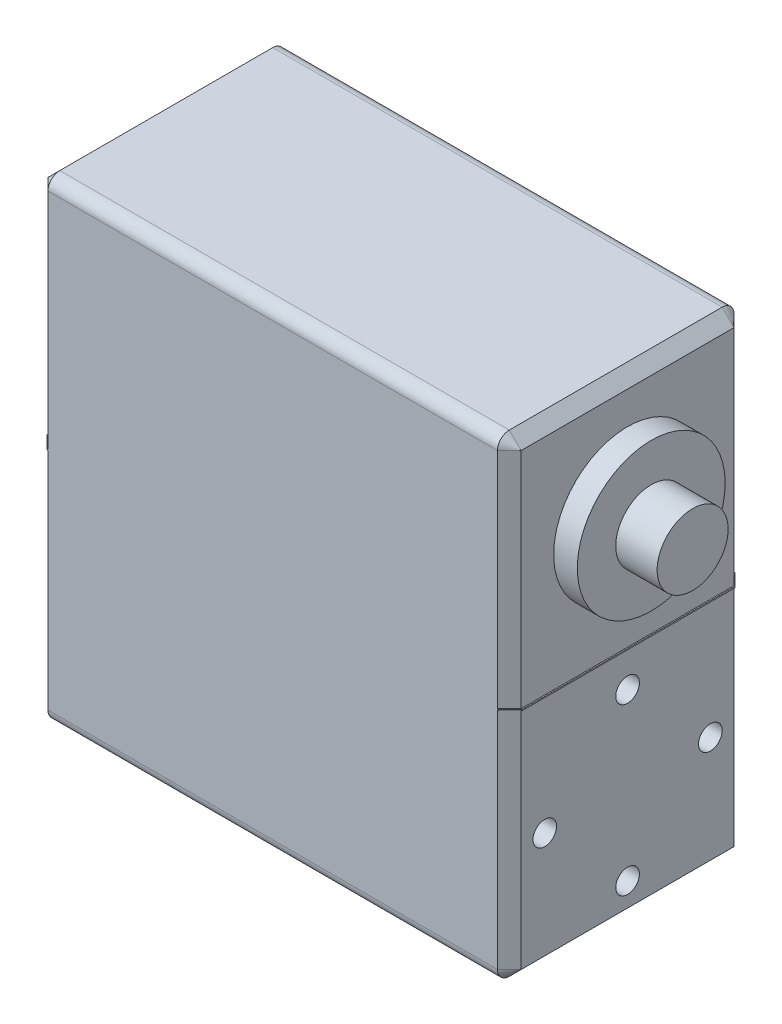
SolidWorks part; units mm, degrees
ref_plane "Спереди" through (0, 0, 0) normal (0, 0, 1) x (1, 0, 0)
ref_plane "Сверху" through (0, 0, 0) normal (0, 1, 0) x (1, 0, 0)
ref_plane "Справа" through (0, 0, 0) normal (1, 0, 0) x (0, 0, -1)
sketch "Sketch1" plane through (0, 0, 0) normal (0, 0, 1) x (1, 0, 0)
  line L0 (0, 0) -> (-20, 20) construction
  line L1 (20, 0) -> (20, 20)
  line L2 (20, 20) -> (-20, 20)
  line L3 (-20, 20) -> (-20, -20)
  line L4 (-20, -20) -> (20, -20)
  line L5 (20, -20) -> (20, 0)
  line L6 (0, 0) -> (20, -20) construction
  line L7 (0, 0) -> (20, 20) construction
  line L8 (0, 0) -> (-20, -20) construction
  dimension "D1" = 40
extrude "Основа" add sketch "Sketch1" along normal blind 20
sketch "Sketch2" plane through (20, 0, 0) normal (1, 0, 0) x (0, 0, -1)
  line L0 (-10, 10) -> (-10, 0) construction
  line L1 (-10, 0) -> (0, 0) construction
  line L2 (0, -20) -> (0, 20) construction
  circle A0 centre (-10, 10) radius 6.25
  dimension "D1" = 12.5
  dimension "D2" = 10
  dimension "D3" = 10
extrude "Выступы под ось" add sketch "Sketch2" along normal blind 2 and the other way blind 42
sketch "Sketch3" plane through (22, 0, 0) normal (1, 0, 0) x (0, 0, -1)
  circle A0 centre (-10, 10) radius 3
  dimension "D1" = 6
extrude "Ось" add sketch "Sketch3" along normal blind 3.5 and the other way blind 47.5
sketch "Sketch5" plane through (-20, 0, 0) normal (-1, 0, 0) x (0, 0, 1)
  line L0 (0, 0) -> (0, 0.1)
  line L1 (20, 20) -> (20, -20) construction
  line L2 (20, 0) -> (0, 0)
  line L3 (0, 20) -> (0, -20) construction
  line L4 (0, 0.1) -> (20, 0.1)
  line L5 (20, 0.1) -> (20, 0)
  dimension "D1" = 0.1
  dimension "D2" = 0.1
extrude "Рейка для выравнивания сборки" add sketch "Sketch5" along normal blind 0.1 and the other way blind 40.1
sketch "Sketch7" plane through (0, 0, 0) normal (0, 0, -1) x (-1, 0, 0)
  line L0 (0, 0) -> (-14, 0) construction
  text T0 "RDS315mg"
  dimension "D1" = 14
extrude "Модель сервы" cut sketch "Sketch7" against normal blind 0.3
fillet "Fillet1" radius 1 4 edges at (0, -20, 20) (0, -20, 0) (0, 20, 20) (0, 20, 0)
chamfer "Chamfer1" distance 1 angle 45 20 edges at (20, -19.7071, 0.2929) (20, -9.5, 0) (20, -20, 10) (20, -19.7071, 19.7071) (20, -9.5, 20) (20, 9.55, 0) (20, 19.7071, 0.2929) (20, 9.55, 20) (20, 19.7071, 19.7071) (20, 20, 10) (-20, -9.5, 20) (-20, -19.7071, 19.7071) (-20, -20, 10) (-20, -19.7071, 0.2929) (-20, -9.5, 0) (-20, 9.55, 20) (-20, 19.7071, 19.7071) (-20, 20, 10) (-20, 19.7071, 0.2929) (-20, 9.55, 0)
chamfer "Chamfer2" distance 1 angle 45 4 edges at (20.1, 0.05, 0) (20.1, 0.05, 20) (-20.1, 0.05, 20) (-20.1, 0.05, 0)
sketch "Эскиз1" plane through (20, 0, 0) normal (1, 0, 0) x (0, 0, -1)
  line L0 (-1, -20) -> (-19, -20) construction
  line L2 (-20, -19) -> (-20, 0) construction
  circle A0 centre (-10, -10) radius 7 construction
  circle A1 centre (-10, -10) radius 8 construction
  circle A2 centre (-10, -3) radius 1
  circle A3 centre (-3, -10) radius 1
  circle A4 centre (-10, -17) radius 1
  circle A5 centre (-17, -10) radius 1
  dimension "D1" = 14
  dimension "D2" = 16
  dimension "D3" = 10
  dimension "D4" = 10
extrude "Вырез-Вытянуть1" cut sketch "Эскиз1" against normal blind 2
sketch "Эскиз2" plane through (-20, 0, 0) normal (-1, 0, 0) x (0, 0, 1)
  line L0 (19, -20) -> (1, -20) construction
  line L1 (2.5, -17.5) -> (17.5, -17.5) construction
  line L2 (2.5, -17.5) -> (2.5, -2.5) construction
  line L3 (2.5, -2.5) -> (17.5, -2.5) construction
  line L4 (17.5, -17.5) -> (17.5, -2.5) construction
  line L5 (0, -19) -> (0, 0) construction
  line L6 (1, 0) -> (1, -19) construction
  line L7 (19, -19) -> (1, -19) construction
  line L8 (19, -19) -> (19, -1) construction
  line L10 (1, -19) -> (1, -2) construction
  circle A0 centre (2.5, -17.5) radius 1
  circle A1 centre (17.5, -17.5) radius 1
  circle A2 centre (17.5, -2.5) radius 1
  circle A3 centre (2.5, -2.5) radius 1
  dimension "D1" = 15
  dimension "D2" = 2.5
  dimension "D3" = 2.5
extrude "Вырез-Вытянуть2" cut sketch "Эскиз2" against normal blind 2
